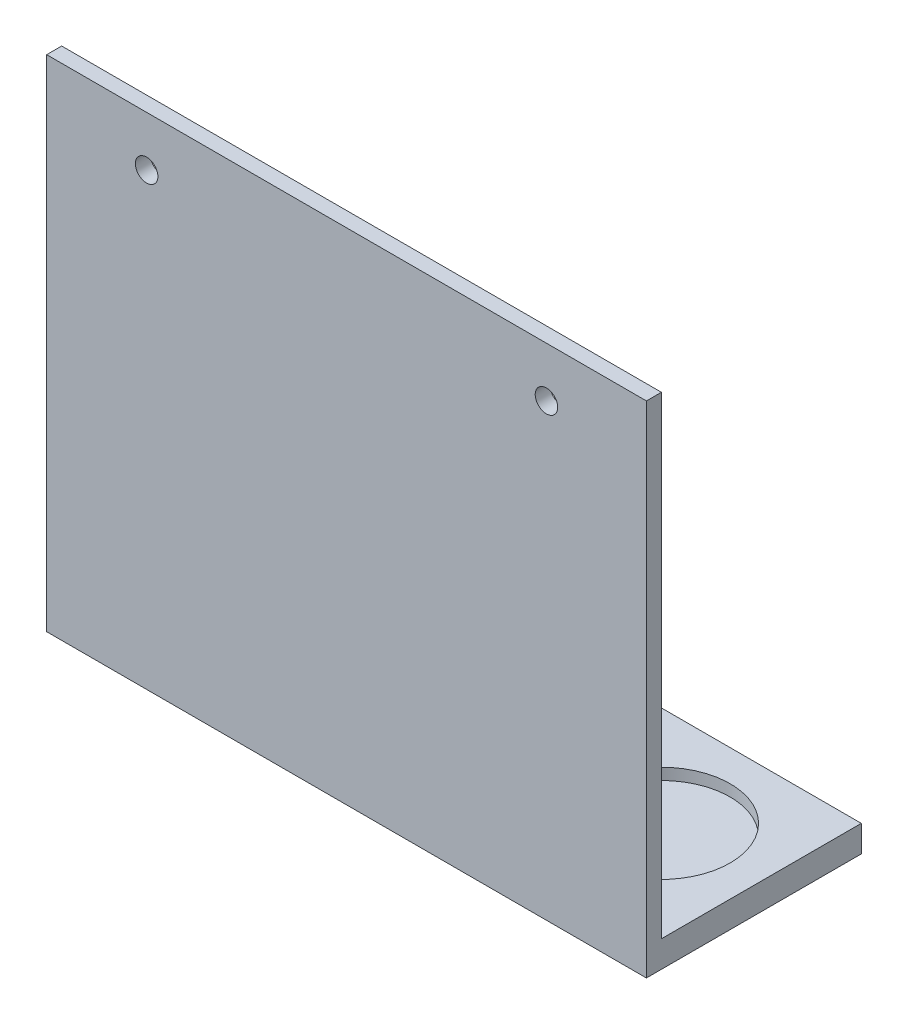
SolidWorks part; units mm, degrees
ref_plane "Front Plane" through (0, 0, 0) normal (0, 0, 1) x (1, 0, 0)
ref_plane "Top Plane" through (0, 0, 0) normal (0, 1, 0) x (1, 0, 0)
ref_plane "Right Plane" through (0, 0, 0) normal (1, 0, 0) x (0, 0, -1)
sketch "Sketch1" plane through (0, 0, 0) normal (1, 0, 0) x (0, 0, -1)
  line L7 (0, -33) -> (3, -33)
  line L8 (3, 67) -> (3, -33)
  line L9 (3, 67) -> (0, 67)
  line L10 (0, 67) -> (0, -33)
  dimension "D4" = 3
  dimension "D5" = 100
extrude "Boss-Extrude1" add sketch "Sketch1" along normal blind 120 contours L9 | L8 L9 L7 region at (0, 17, -1.5)
sketch "Sketch8" plane through (0, 0, 0) normal (0, 0, 1) x (1, 0, 0)
  line L0 (0, 67) -> (0, -33) construction
  line L1 (120, 67) -> (120, -33) construction
  line L2 (120, 67) -> (0, 67) construction
  circle A0 centre (20, 57) radius 2.25
  circle A1 centre (100, 57) radius 2.25
  dimension "D1" = 20
  dimension "D2" = 20
  dimension "D3" = 10
  dimension "D4" = 10
  dimension "D5" = 4.5
  dimension "D6" = 4.5
extrude "Cut-Extrude4" cut sketch "Sketch8" against normal blind 15
sketch "Sketch9" plane through (0, 0, -3) normal (0, 0, -1) x (-1, 0, 0)
  line L0 (0, 67) -> (0, -33) construction
  line L1 (-120, -33) -> (0, -33)
  line L2 (-120, -33) -> (-120, -30)
  line L3 (-120, -30) -> (0, -30)
  line L4 (0, -33) -> (0, -30)
  dimension "D1" = 3
extrude "Boss-Extrude2" add sketch "Sketch9" along normal blind 40
sketch "Sketch10" plane through (0, -30, 0) normal (0, 1, 0) x (1, 0, 0)
  line L0 (120, 43) -> (120, 3) construction
  line L2 (120, 43) -> (0, 43)
  line L3 (120, 43) -> (120, 3)
  line L4 (120, 3) -> (0, 3)
  line L5 (0, 43) -> (0, 3)
  circle A0 centre (100, 23) radius 13.75
  circle A1 centre (63, 23) radius 7.6
  circle A2 centre (26, 23) radius 7.6
  circle A3 centre (6, 23) radius 2.26
  point P5 (120, 23)
  dimension "D1" = 27.5
  dimension "D2" = 20
  dimension "D3" = 15.2
  dimension "D4" = 15.2
  dimension "D5" = 37
  dimension "D6" = 37
  dimension "D7" = 4.52
  dimension "D8" = 20
extrude "Boss-Extrude3" add sketch "Sketch10" along normal blind 2.3
sketch "Sketch11" plane through (0, -30, 0) normal (0, 1, 0) x (1, 0, 0)
  circle A0 centre (63, 23) radius 7
  circle A1 centre (26, 23) radius 2.25
  circle A2 centre (6, 23) radius 2.26
  dimension "D1" = 14
  dimension "D2" = 4.5
extrude "Cut-Extrude5" cut sketch "Sketch11" against normal through all
